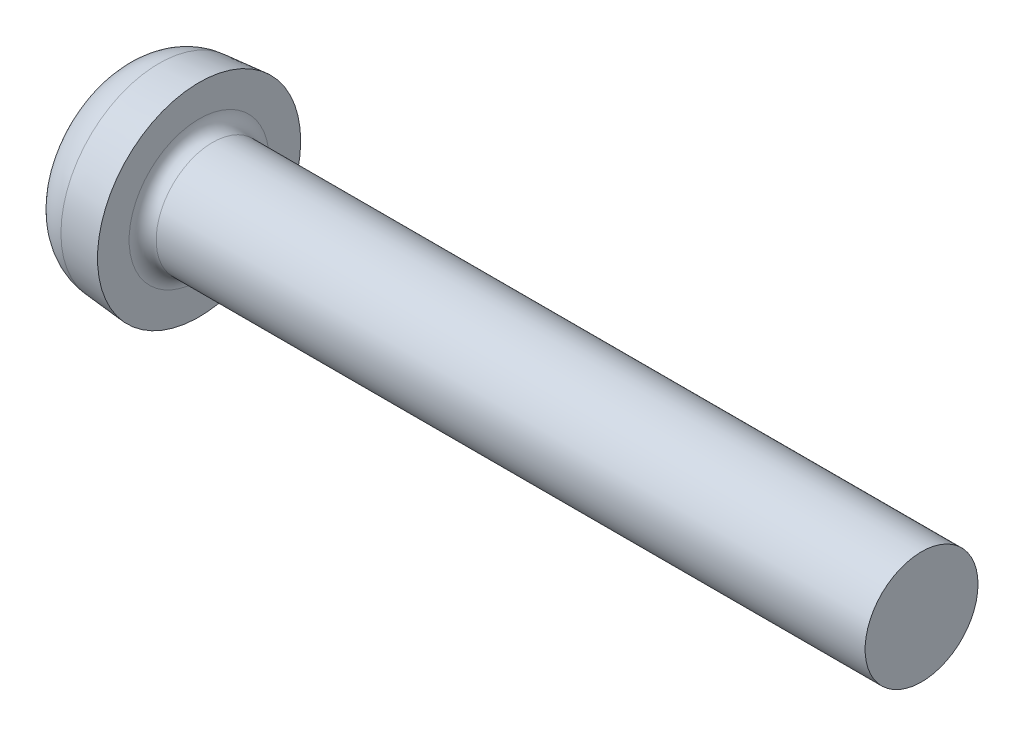
SolidWorks part; units mm, degrees
ref_plane "Front" through (0, 0, 0) normal (0, 0, 1) x (1, 0, 0)
ref_plane "Top" through (0, 0, 0) normal (0, 1, 0) x (1, 0, 0)
ref_plane "Right" through (0, 0, 0) normal (1, 0, 0) x (0, 0, -1)
sketch "Sketch1" plane through (0, 0, 0) normal (0, 0, 1) x (1, 0, 0)
  line L0 (17.8, 1.25) -> (2.7, 1.25)
  line L1 (1.8, 1.55) -> (1.8, 2.25)
  line L2 (1.8, 2.25) -> (0, 2.0925)
  line L3 (2.7, 1.25) -> (2.1, 1.25)
  line L4 (17.8, 1.25) -> (17.8, 0)
  line L5 (4.5158, 0) -> (-13.5157, 0) construction
  line L6 (17.8, 0) -> (0, 0)
  line L7 (0, 0) -> (0, 2.0925)
  arc A1 (1.8, 1.55) -> (2.1, 1.25) centre (2.1, 1.55) ccw
  dimension "D2" = 95
  dimension "k" = 1.8
  dimension "dk" = 4.5
revolve "Base" add sketch "Sketch1" angle 360 about L5
cosmetic thread "ThreadCosmetic1" parameters "bb"=16
sketch "Sketch6" plane through (0, 0, 0) normal (1, 0, 0) x (0, 0, -1)
  line L0 (-1.9271, 0) -> (2.0512, 0) construction
  line L1 (0, 1.8651) -> (0, -2.0207) construction
  line L2 (0.27, 0.27) -> (0.27, 1.35)
  line L3 (0.27, 1.35) -> (-0.27, 1.35)
  line L4 (-0.27, 0.27) -> (-0.27, 1.35)
  line L5 (0.27, 0.27) -> (1.35, 0.27)
  line L6 (1.35, 0.27) -> (1.35, -0.27)
  line L7 (-1.35, 0.27) -> (-1.35, -0.27)
  line L8 (-0.27, 0.27) -> (-1.35, 0.27)
  line L9 (-0.27, -0.27) -> (-1.35, -0.27)
  line L10 (0.27, -0.27) -> (1.35, -0.27)
  line L11 (-0.27, -0.27) -> (-0.27, -1.35)
  line L12 (0.27, -1.35) -> (-0.27, -1.35)
  line L13 (0.27, -0.27) -> (0.27, -1.35)
  point P16 (-1.35, 0)
  point P17 (1.35, 0)
extrude "CrossRecess" cut sketch "Sketch6" along normal blind 1.8
fillet "Fillet5" radius 0.3 4 edges at (0.9, -0.27, 0.27) (0.9, -0.27, -0.27) (0.9, 0.27, 0.27) (0.9, 0.27, -0.27)
sketch "Sketch8" [suppressed] plane through (0, 0, 0) normal (0, 0, 1) x (1, 0, 0)
  line L0 (12, 4) -> (8.2, 3.5)
  line L1 (8.2, 3.5) -> (5, 3.5)
  line L3 (50, -4) -> (50, 4) construction
  line L4 (5, -6.5) -> (5, 6.5) construction
  line L6 (5, 3.5) -> (5, 14)
  line L7 (5, 14) -> (12, 14)
  line L8 (12, 14) -> (12, 4)
  line L9 (52.4753, 0) -> (42.9594, 0) construction
  dimension "D1" = 22.5
fillet "HeadFillet" radius 1 1 edges at (0, 0, -2.0925)
draft "Draft1" type of draft neutral plane draft angle 20 faces to draft 4 face at (0.9102, -0.0675, 1.35) face at (0.9102, -1.35, -0.0675) face at (0.9102, 0.0675, -1.35) face at (0.9102, 1.35, 0.0675) neutral plane through (0, 0, 0) neutral plane normal (-1, 0, 0) parameters "D1"=20
sketch "Sketch7" plane through (0, 0, 0) normal (1, 0, 0) x (0, 0, -1)
  line L0 (-8.3217, 0) -> (7.4212, 0) construction
  line L1 (0, 7.4989) -> (0, -7.9646) construction
  line L2 (0, 0) -> (6.8599, 6.8599) construction
  line L3 (0.9546, 0.9546) -> (0, 0.5095)
  line L4 (0, 0) -> (-6.8599, 6.8599) construction
  line L5 (0.9546, 0.9546) -> (0.5095, 0)
  line L6 (0.9546, -0.9546) -> (0, -0.5095)
  line L7 (0.9546, -0.9546) -> (0.5095, 0)
  line L8 (-0.9546, -0.9546) -> (0, -0.5095)
  line L9 (-0.9546, -0.9546) -> (-0.5095, 0)
  line L10 (-0.9546, 0.9546) -> (0, 0.5095)
  line L11 (-0.9546, 0.9546) -> (-0.5095, 0)
  dimension "D2" = 20
extrude "Cut-Extrude3" [suppressed] cut sketch "Sketch7" along normal blind 10 draft 20
sketch "Sketch10" plane through (0, 0, 0) normal (0, 0, 1) x (1, 0, 0)
  line L0 (17.8, 1.0391) -> (17.9217, 1.25)
  line L1 (17.9217, 1.25) -> (17.9217, 1.4935)
  line L2 (17.9217, 1.4935) -> (17.6782, 1.4935)
  line L3 (17.6782, 1.4935) -> (17.6782, 1.25)
  line L4 (17.6782, 1.25) -> (17.8, 1.0391)
  line L5 (17.8, 1.25) -> (2.7, 1.25) construction
  line L6 (17.8, 1.25) -> (17.8, 0) construction
  line L7 (0, 0) -> (57.111, 0) construction
  dimension "D1" = 0.2435
revolve "Cut-Revolve10" [suppressed] cut sketch "Sketch10" angle 360 about L7
pattern_linear "LPattern10" [suppressed] count 55 spacing 0.2922 along (-1, 0, 0) of bodies 107
equation "\"D1@Sketch6\" = \"m@Sketch6\" / 5"
equation "\"D1@Sketch8\" = \"d@Sketch8\" + 20"
equation "\"D1@Sketch10\" =  ( \"d@Sketch1\" - \"THD_MINOR@ThreadCosmetic1\" )  / 2"
equation "\"D3@LPattern10\" = \"D1@Sketch10\" * 1.2"
equation "\"D1@LPattern10\" = \"bb@ThreadCosmetic1\" / \"D3@LPattern10\" "
